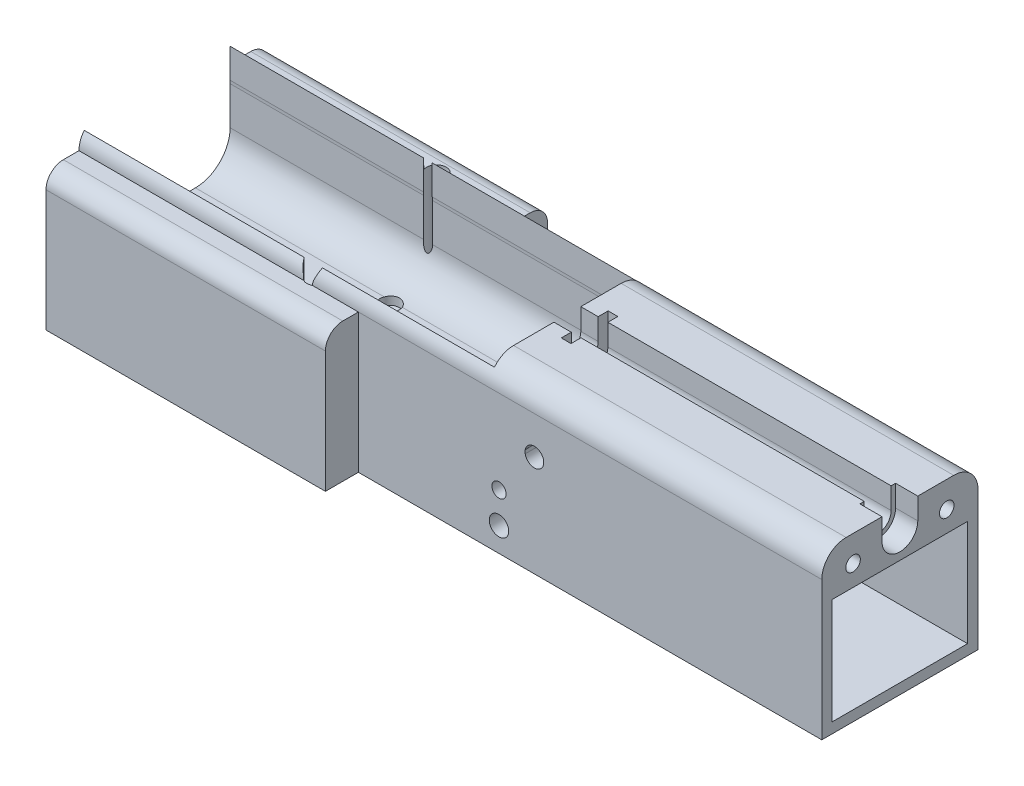
SolidWorks part; units mm, degrees
other "Markup1"
sketch "Sketch10" plane through (217, 42, -42) normal (0.057, 0.9883, -0.1416) x (-0.9984, 0.0574, -0.0017)
ref_plane "Front Plane" through (0, 0, 0) normal (0, 0, 1) x (1, 0, 0)
ref_plane "Top Plane" through (0, 0, 0) normal (0, 1, 0) x (1, 0, 0)
ref_plane "Right Plane" through (0, 0, 0) normal (1, 0, 0) x (0, 0, -1)
sketch "Sketch1" plane through (0, 0, 0) normal (0, 1, 0) x (1, 0, 0)
  line L1 (0, 0) -> (223, 0)
  line L2 (0, 0) -> (0, 45)
  line L3 (0, 45) -> (223, 45)
  line L4 (223, 0) -> (223, 45)
  dimension "D1" = 45
  dimension "D2" = 223
extrude "Boss-Extrude1" add sketch "Sketch1" along normal blind 42
sketch "Sketch4" plane through (223, 0, 0) normal (1, 0, 0) x (0, 0, -1)
  line L0 (0, 42) -> (45, 42) construction
  line L1 (18.625, 42) -> (26.375, 42)
  line L2 (18.625, 42) -> (18.625, 35.825)
  line L3 (18.625, 35.825) -> (26.375, 35.825)
  line L4 (26.375, 42) -> (26.375, 35.825)
  line L5 (0, 42) -> (0, 0) construction
  dimension "D4" = 6.175
  dimension "D1" = 0
  dimension "D2" = 18.625
  dimension "D3" = 7.75
extrude "Cut-Extrude14" cut sketch "Sketch4" against normal blind 95.8
sketch "Sketch5" plane through (223, 0, 0) normal (1, 0, 0) x (0, 0, -1)
  line L2 (0, 42) -> (0, 0) construction
  line L4 (18.625, 35.825) -> (26.375, 35.825) construction
  circle A0 centre (22.5, 35.825) radius 3.875
  dimension "D1" = 0
  dimension "D2" = 22.5
extrude "Cut-Extrude15" cut sketch "Sketch5" against normal blind 95.8
sketch "Sketch6" plane through (0, 0, 0) normal (-1, 0, 0) x (0, 0, 1)
  line L0 (-45, 42) -> (0, 42) construction
  line L1 (-45, 42) -> (-45, 0) construction
  line L2 (-38, 36.5) -> (-7, 36.5) construction
  circle A0 centre (-38, 36.5) radius 1.5
  circle A1 centre (-7, 36.5) radius 1.5
  circle A2 centre (-6.9093, 5.5026) radius 1.5
  circle A3 centre (-37.9093, 5.5026) radius 1.5
  dimension "D1" = 5.5
  dimension "D6" = 3
  dimension "D2" = 7
  dimension "D5" = 31
  dimension "D3" = 2
  dimension "D4" = 2
extrude "Cut-Extrude16" [suppressed] cut sketch "Sketch6" against normal blind 7
sketch "Sketch7" plane through (0, 42, 0) normal (0, 1, 0) x (1, 0, 0)
  line L0 (223, 45) -> (0, 45) construction
  line L1 (9, 43.5) -> (127.2, 43.5)
  line L2 (9, 43.5) -> (9, 1.5)
  line L3 (9, 1.5) -> (127.2, 1.5)
  line L4 (127.2, 43.5) -> (127.2, 1.5)
  line L5 (0, 0) -> (223, 0) construction
  line L7 (0, 45) -> (0, 0) construction
  dimension "D1" = 1.5
  dimension "D2" = 1.5
  dimension "D3" = 9
  dimension "D4" = 118.2
extrude "Cut-Extrude17" cut sketch "Sketch7" against normal blind 21
ref_plane "Front" through (0, 21, 0) normal (0, 1, 0) x (1, 0, 0)
ref_plane "Top" through (127.2, 0, 0) normal (-1, 0, 0) x (0, 0, 1)
ref_plane "Right" through (0, 0, -22.5) normal (0, 0, 1) x (1, 0, 0)
sketch "Sketch8" plane through (9, 0, 0) normal (-1, 0, 0) x (0, 0, 1)
  line L0 (-7.5741, 31) -> (-37.4259, 31)
  line L1 (-37.507, 11) -> (-7.493, 11)
  line L2 (-45, 42) -> (0, 42) construction
  line L3 (-45, 0) -> (0, 0) construction
  line L4 (-45, 42) -> (-45, 0) construction
  arc A0 (-37.4259, 31) -> (-37.507, 11) centre (-22.5, 20.9393) ccw
  arc A1 (-7.493, 11) -> (-7.5741, 31) centre (-22.5, 20.9393) ccw
  dimension "D3" = 22.5
  dimension "D4" = 29.8518
  dimension "D5" = 18
  dimension "D1" = 11
  dimension "D2" = 11
extrude "Cut-Extrude18" [suppressed] cut sketch "Sketch8" against normal up to vertex
sketch "Sketch11" plane through (0, 42, 0) normal (0, 1, 0) x (1, 0, 0)
  line L0 (127.2, 26.375) -> (127.2, 43.5) construction
  line L1 (132.2, 29.25) -> (135, 29.25)
  line L2 (132.2, 29.25) -> (132.2, 15.75)
  line L3 (132.2, 15.75) -> (135, 15.75)
  line L4 (135, 29.25) -> (135, 15.75)
  line L5 (223, 45) -> (0, 45) construction
  dimension "D1" = 5
  dimension "D2" = 13.5
  dimension "D3" = 15.75
  dimension "D4" = 2.8
extrude "Cut-Extrude19" cut sketch "Sketch11" against normal blind 11.5
sketch "Sketch13" plane through (127.2, 0, 0) normal (-1, 0, 0) x (0, 0, 1)
  line L0 (-1.5, 21) -> (-1.5, 42) construction
  line L1 (-26.375, 42) -> (-43.5, 42) construction
  circle A0 centre (-22.5, 21) radius 5.5
  dimension "D1" = 11
  dimension "D2" = 21
  dimension "D3" = 21
extrude "Cut-Extrude20" [suppressed] cut sketch "Sketch13" against normal blind 10 and the other way up to surface
sketch "Sketch54" [suppressed] plane through (0, 0, 0) normal (-1, 0, 0) x (0, 0, 1)
  circle A0 centre (-22.4093, 21.0026) radius 11.25
  circle A1 centre (-37.9093, 5.5026) radius 1.5 construction
  circle A3 centre (-6.9093, 5.5026) radius 1.5 construction
  dimension "D1" = 22.5
  dimension "D2" = 15.5
  dimension "D3" = 15.5
extrude "Cut-Extrude45" [suppressed] cut sketch "Sketch54" against normal blind 9
sketch "Sketch14" plane through (0, 0, 0) normal (0, -1, 0) x (1, 0, 0)
  line L0 (0, -45) -> (0, 0) construction
  line L1 (9, -54.5) -> (89.5, -54.5)
  line L2 (9, -54.5) -> (9, -45)
  line L3 (9, 9.5) -> (89.5, 9.5)
  line L4 (89.5, -54.5) -> (89.5, -45)
  line L5 (223, -45) -> (0, -45) construction
  line L6 (89.5, -45) -> (223, -45)
  line L7 (223, -45) -> (223, 0)
  line L8 (223, 0) -> (89.5, 0)
  line L9 (0, 0) -> (223, 0) construction
  line L10 (9, 0) -> (0, 0)
  line L11 (0, 0) -> (0, -45)
  line L12 (0, -45) -> (9, -45)
  line L13 (9, 0) -> (9, 9.5)
  line L14 (89.5, 0) -> (89.5, 9.5)
  point P6 (0, -22.5)
  dimension "D1" = 64
  dimension "D2" = 80.5
  dimension "D3" = 9
  dimension "D4" = 9.5
extrude "Boss-Extrude2" add sketch "Sketch14" along normal blind 5
sketch "Sketch42" plane through (0, 0, 0) normal (0, 1, 0) x (1, 0, 0)
  line L0 (89.5, 0) -> (89.5, -9.5)
  line L1 (9, 45) -> (89.5, 45)
  line L2 (9, 45) -> (9, 54.5)
  line L3 (9, 54.5) -> (89.5, 54.5)
  line L4 (89.5, 45) -> (89.5, 54.5)
  line L5 (89.5, -9.5) -> (9, -9.5)
  line L6 (9, -9.5) -> (9, 0)
  line L7 (9, 0) -> (89.5, 0)
extrude "Boss-Extrude3" add sketch "Sketch42" along normal blind 35
sketch "Sketch27" [suppressed] plane through (9, 0, 0) normal (1, 0, 0) x (0, 0, -1)
  circle A0 centre (7, 36.5) radius 2.775
  circle A1 centre (38, 36.5) radius 2.775
  dimension "D1" = 2
extrude "Cut-Extrude28" [suppressed] cut sketch "Sketch27" against normal blind 3.1
extrude "Cut-Extrude32" cut sketch "Sketch38" against normal blind 4.7
sketch "Sketch38" plane through (127.2, -5, -22.5) normal (0, -1, 0) x (0, 0, -1)
  circle A3 centre (23.5, -61.2) radius 3.1
  circle A6 centre (10, -61.2) radius 3.1
extrude "Cut-Extrude35" cut sketch "Sketch41" against normal blind 4
sketch "Sketch41" plane through (127.2, -5, -22.5) normal (0, -1, 0) x (0, 0, -1)
  circle A3 centre (20, -73.2) radius 5.75
  circle A6 centre (-20, -73.2) radius 5.75
fillet "Fillet1" radius 7 2 edges at (111.5, 42, -45) (111.5, 42, 0)
fillet "Fillet7" radius 5 2 edges at (49.25, 35, -54.5) (49.25, 35, 9.5)
extrude "Cut-Extrude39" cut sketch "Sketch47" against normal blind 7
sketch "Sketch47" plane through (127.2, -0.3, -22.5) normal (0, -1, 0) x (0, 0, -1)
  circle A0 centre (23.5, -61.2) radius 1.5
  circle A1 centre (10, -61.2) radius 1.5
sketch "Sketch49" plane through (0, 6.7, 0) normal (0, -1, 0) x (1, 0, 0)
  circle A0 centre (66, -32.5) radius 2.8
  circle A1 centre (66, -46) radius 2.8
  dimension "D1" = 5.6
extrude "Cut-Extrude41" cut sketch "Sketch49" against normal blind 33
sketch "Sketch52" plane through (223, 0, 0) normal (1, 0, 0) x (0, 0, -1)
  line L0 (17.35, 42) -> (17.35, 35.82)
  line L1 (7, 42) -> (18.625, 42) construction
  line L2 (26.375, 42) -> (38, 42) construction
  line L3 (27.65, 42) -> (27.65, 35.82)
  line L4 (22.5, 35.82) -> (22.5, 42) construction
  line L5 (17.35, 42) -> (27.65, 42)
  line L6 (17.35, 35.82) -> (0, 35.82) construction
  line L7 (0, 35) -> (0, -5) construction
  line L8 (27.65, 35.82) -> (45, 35.82) construction
  line L9 (45, 35) -> (45, -5) construction
  arc A0 (17.35, 35.82) -> (27.65, 35.82) centre (22.5, 35.82) ccw
  dimension "D1" = 10.3
  dimension "D2" = 6.18
extrude "Cut-Extrude43" cut sketch "Sketch52" against normal blind 6.4
sketch "Sketch53" plane through (223, 0, 0) normal (1, 0, 0) x (0, 0, -1)
  line L0 (7, 42) -> (17.35, 42) construction
  line L1 (27.65, 42) -> (38, 42) construction
  circle A0 centre (9, 34.5) radius 2.1
  circle A1 centre (36, 34.5) radius 2.1
  arc A2 (17.35, 35.82) -> (27.65, 35.82) centre (22.5, 35.82) ccw construction
  arc A3 (17.35, 35.82) -> (27.65, 35.82) centre (22.5, 35.82) ccw construction
  dimension "D2" = 7.5
  dimension "D4" = 13.5
  dimension "D5" = 4.2
  dimension "D1" = 7.5
  dimension "D3" = 13.5
extrude "Cut-Extrude44" cut sketch "Sketch53" against normal blind 95
sketch "Sketch55" plane through (223, 0, 0) normal (1, 0, 0) x (0, 0, -1)
  line L0 (42, -2) -> (42, 28.52)
  line L2 (42, 28.52) -> (3, 28.52)
  line L3 (3, 28.52) -> (3, -2)
  line L4 (3, -2) -> (42, -2)
  line L5 (45, 35) -> (45, -5) construction
  line L6 (45, -5) -> (0, -5) construction
  line L7 (0, 35) -> (0, -5) construction
  arc A1 (17.35, 35.82) -> (27.65, 35.82) centre (22.5, 35.82) ccw construction
  dimension "D1" = 3
  dimension "D2" = 3
  dimension "D3" = 3
  dimension "D4" = 7.3
extrude "Cut-Extrude46" cut sketch "Sketch55" against normal blind 55
sketch "Sketch56" plane through (0, -5, 0) normal (0, -1, 0) x (1, 0, 0)
  line L0 (127.2, -9) -> (127.2, -19.4)
  line L1 (127.2, -19.4) -> (143, -19.4)
  line L2 (143, -19.4) -> (143, -9)
  line L3 (143, -9) -> (127.2, -9)
  line L4 (0, 0) -> (0, -45) construction
  line L5 (223, 0) -> (89.5, 0) construction
  dimension "D1" = 127.2
  dimension "D2" = 10.4
  dimension "D3" = 15.8
  dimension "D4" = 9
extrude "Cut-Extrude47" cut sketch "Sketch56" against normal blind 32.15
sketch "Sketch57" plane through (0, -5, 0) normal (0, -1, 0) x (1, 0, 0)
  line L6 (127.2, -9) -> (127.2, -19.4) construction
  line L7 (127.2, -9) -> (122.2, -9)
  line L8 (127.2, -9) -> (127.2, -19.4)
  line L9 (127.2, -19.4) -> (122.2, -19.4)
  line L10 (122.2, -9) -> (122.2, -19.4)
  line L11 (143, -9) -> (127.2, -9) construction
  line L12 (127.2, -19.4) -> (143, -19.4) construction
  dimension "D4" = 5
extrude "Cut-Extrude48" cut sketch "Sketch57" against normal blind 15
extrude "Cut-Extrude49" cut sketch "Sketch58" against normal blind 10
sketch "Sketch58" plane through (127.2, 21, 0) normal (0, 0, 1) x (0, -1, 0)
  line L6 (-2.6328, 15.65) -> (-3.6672, 15.65)
  line L7 (-3.6672, 10.35) -> (-2.6328, 10.35)
  circle A4 centre (19.05, 2.8) radius 2.8
  circle A6 centre (10.15, 2.8) radius 2.05
  arc A12 (-2.6328, 10.35) -> (-2.6328, 15.65) centre (-3.15, 13) ccw
  arc A13 (-3.6672, 15.65) -> (-3.6672, 10.35) centre (-3.15, 13) ccw
sketch "Sketch59" plane through (0, 0, -19.4) normal (0, 0, 1) x (1, 0, 0)
  line L2 (137.55, 24.6672) -> (137.55, 23.6328) construction
  circle A0 centre (130, 1.95) radius 1.5
  circle A1 centre (130, 10.85) radius 0.95
  circle A2 centre (140.2, 24.15) radius 1.5
  circle A3 centre (130, 1.95) radius 2.8 construction
  circle A4 centre (130, 10.85) radius 2.05 construction
  arc A7 (142.85, 24.6672) -> (137.55, 24.6672) centre (140.2, 24.15) ccw construction
  dimension "D1" = 3
  dimension "D2" = 1.9
  dimension "D3" = 2.65
  dimension "D4" = 3
  dimension "D5" = 1.2
extrude "Cut-Extrude50" cut sketch "Sketch59" against normal blind 6.5
sketch "Sketch62" plane through (0, 0, 0) normal (-1, 0, 0) x (0, 0, 1)
  line L0 (0, -5) -> (-45, -5)
  line L1 (-45, -5) -> (-45, 35)
  line L3 (-38, 42) -> (-7, 42)
  line L4 (-38, 42) -> (-7, 42) construction
  line L5 (0, 35) -> (0, -5)
  arc A0 (0, 35) -> (-7, 42) centre (-7, 35) ccw
  arc A1 (-45, 35) -> (-38, 42) centre (-38, 35) cw
  point P13 (0, 42)
  dimension "D1" = 7
extrude "Cut-Extrude51" cut sketch "Sketch62" against normal blind 9
extrude "Cut-Extrude52" cut sketch "Sketch63" along normal blind 118.2
sketch "Sketch63" plane through (127.2, 21, -22.5) normal (-1, 0, 0) x (0, 0, -1)
  line L12 (-10.9597, -18.9503) -> (11.0403, -18.9503)
  line L17 (21.0403, -8.9503) -> (21.0403, 2.0497)
  line L18 (11.0403, 12.0497) -> (-10.9597, 12.0497)
  line L19 (-20.9597, 2.0497) -> (-20.9597, -8.9503)
  arc A16 (11.0403, -18.9503) -> (21.0403, -8.9503) centre (11.0403, -8.9503) ccw
  arc A17 (21.0403, 2.0497) -> (11.0403, 12.0497) centre (11.0403, 2.0497) ccw
  arc A18 (-10.9597, 12.0497) -> (-20.9597, 2.0497) centre (-10.9597, 2.0497) ccw
  arc A19 (-20.9597, -8.9503) -> (-10.9597, -18.9503) centre (-10.9597, -8.9503) ccw
extrude "Cut-Extrude53" cut sketch "Sketch64" against normal blind 14
sketch "Sketch64" plane through (127.2, -5, -22.5) normal (0, -1, 0) x (0, 0, -1)
  circle A3 centre (-1, -71.2) radius 1.5
extrude "Cut-Extrude54" cut sketch "Sketch65" against normal blind 9.95
sketch "Sketch65" plane through (127.2, 8.9503, -22.5) normal (0, 1, 0) x (0, 0, 1)
  circle A1 centre (1, -71.2) radius 2.8
extrude "Cut-Extrude55" cut sketch "Sketch66" against normal blind 25
sketch "Sketch66" plane through (127.2, -5, -22.5) normal (0, -1, 0) x (0, 0, -1)
  circle A3 centre (-20, -52.2) radius 1.5
extrude "Cut-Extrude56" cut sketch "Sketch67" against normal blind 7
sketch "Sketch67" plane through (9, 21, -22.5) normal (-1, 0, 0) x (0, 0, -1)
  circle A3 centre (27, -9) radius 1.45
  circle A6 centre (27, 21) radius 1.45
  circle A9 centre (-27, 21) radius 1.45
  circle A12 centre (-27, -9) radius 1.45
sketch "Sketch68" plane through (127.2, 0, 0) normal (-1, 0, 0) x (0, 0, 1)
  circle A0 centre (-9, 34.5) radius 2.6
  circle A1 centre (-36, 34.5) radius 2.6
  dimension "D1" = 5.2
extrude "Cut-Extrude57" cut sketch "Sketch68" against normal blind 28.3
extrude "Cut-Extrude59" cut sketch "Sketch70" against normal blind 8
sketch "Sketch70" plane through (127.2, -5, -22.5) normal (0, -1, 0) x (0, 0, -1)
  circle A3 centre (0, -33.7) radius 5.5
extrude "Cut-Extrude60" cut sketch "Sketch71" along normal blind 42 from offset 4
sketch "Sketch71" plane through (127.2, -5, -22.5) normal (0, 1, 0) x (0, 0, 1)
  circle A0 centre (20, -52.2) radius 2.8
